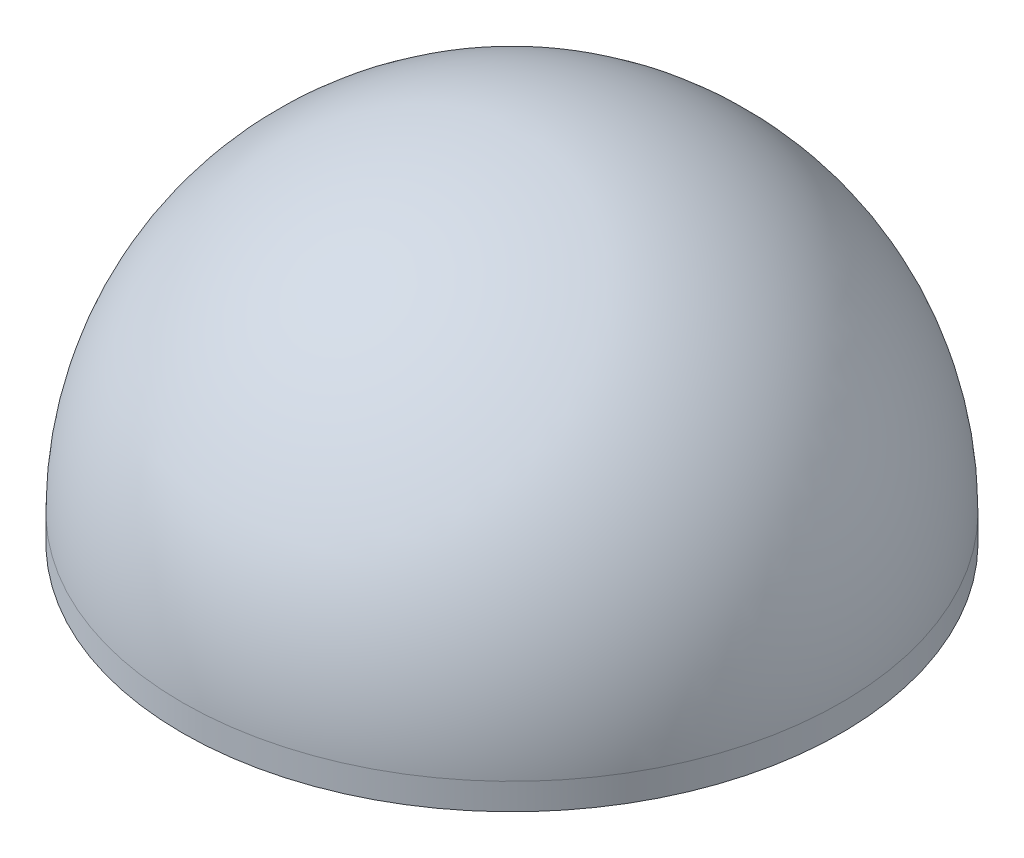
SolidWorks part; units mm, degrees
ref_plane "Front Plane" through (0, 0, 0) normal (0, 0, 1) x (1, 0, 0)
ref_plane "Top Plane" through (0, 0, 0) normal (0, 1, 0) x (1, 0, 0)
ref_plane "Right Plane" through (0, 0, 0) normal (1, 0, 0) x (0, 0, -1)
sketch "Sketch1" plane through (0, 0, 0) normal (0, 1, 0) x (1, 0, 0)
  circle A0 centre (0, 0) radius 25
  dimension "D1" = 50
extrude "Boss-Extrude1" add sketch "Sketch1" along normal blind 2
dome "Dome1" faces to dome 1 distance 25 reverse direction no elliptical dome no face at (0, 2, 25) parameters "D1"=25
shell "Shell1" thickness 2 removed face at (0, 0, 25)
